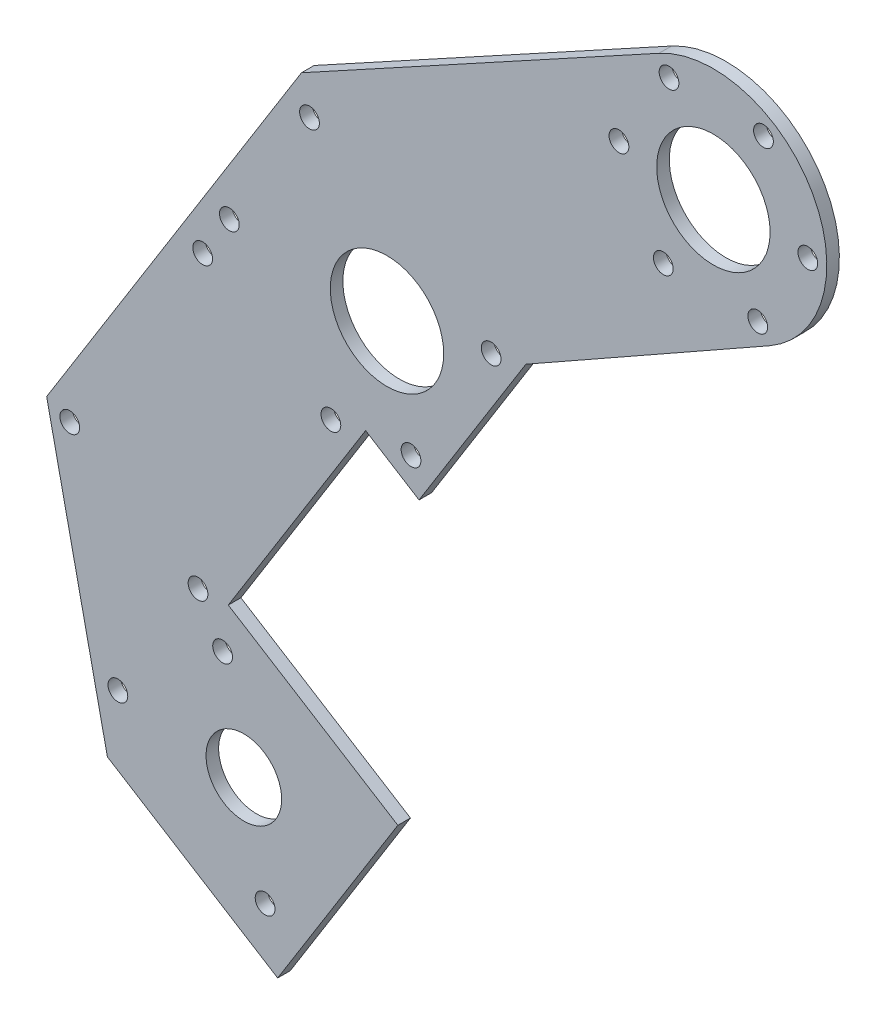
SolidWorks part; units mm, degrees
ref_plane "Front Plane" through (0, 0, 0) normal (0, 0, 1) x (1, 0, 0)
ref_plane "Top Plane" through (0, 0, 0) normal (0, 1, 0) x (1, 0, 0)
ref_plane "Right Plane" through (0, 0, 0) normal (1, 0, 0) x (0, 0, -1)
sketch "Sketch1" plane through (0, 0, -14.1946) normal (0, 0, 1) x (1, 0, 0)
  line L0 (-11.4036, 461.0409) -> (18.8813, 509.5069)
  line L1 (-54.3079, 487.8505) -> (-69.6155, 558.824)
  line L2 (18.8813, 509.5069) -> (-23.8465, 536.2061)
  line L3 (10.7592, 591.5868) -> (-157.4902, 322.3315) construction
  line L4 (-11.4036, 461.0409) -> (-54.3079, 487.8505)
  line L5 (-69.6155, 558.824) -> (-5.4017, 661.5875)
  line L6 (-23.8465, 536.2061) -> (10.7592, 591.5868)
  line L8 (-115.7964, 730.5698) -> (51.1419, 626.2552) construction
  line L9 (-142.7163, 687.4889) -> (24.222, 583.1743) construction
  line L10 (51.1419, 626.2552) -> (112.462, 660.9373)
  line L11 (10.7592, 591.5868) -> (24.222, 583.1743)
  line L13 (24.222, 583.1743) -> (51.1419, 626.2552)
  line L16 (-5.4017, 661.5875) -> (84.678, 710.8773)
  circle A2 centre (16.1415, 618.1747) radius 14.2875
  circle A3 centre (-19.9236, 500.5437) radius 9.525
  circle A5 centre (98.3945, 685.8096) radius 14.2875
  arc A7 (112.462, 660.9373) -> (84.678, 710.8773) centre (98.3945, 685.8096) ccw
  point P33 (98.3945, 685.8096)
extrude "Boss-Extrude1" add sketch "Sketch1" along normal blind 3.175
sketch "Sketch17" plane through (0, 0, -11.0196) normal (0, 0, 1) x (1, 0, 0)
  line L0 (-14.5684, 475.7147) -> (-19.9236, 500.5437)
  line L1 (-19.9236, 500.5437) -> (-25.2787, 525.3728)
  line L2 (16.1415, 618.1747) -> (37.6819, 604.7147) construction
  line L12 (24.222, 583.1743) -> (51.1419, 626.2552) construction
  line L13 (37.6819, 604.7147) -> (27.587, 588.5594) construction
  line L14 (27.587, 588.5594) -> (22.2019, 591.9244) construction
  line L15 (22.2019, 591.9244) -> (-28.9566, 623.8918) construction
  line L16 (-5.4017, 661.5875) -> (-69.6155, 558.824) construction
  line L17 (-28.9566, 623.8918) -> (-23.5715, 620.5268) construction
  line L18 (-23.5715, 620.5268) -> (-3.3816, 652.8374) construction
  line L19 (-3.3816, 652.8374) -> (42.3918, 624.2351) construction
  line L20 (10.7592, 591.5868) -> (5.3741, 594.9518) construction
  line L21 (5.3741, 594.9518) -> (-31.4748, 535.9811) construction
  line L22 (-31.4748, 535.9811) -> (-51.6648, 503.6705) construction
  line L23 (5.3741, 594.9518) -> (2.0091, 589.5667) construction
  line L24 (-31.4748, 535.9811) -> (-63.7855, 556.1711) construction
  line L25 (2.0091, 589.5667) -> (-30.3015, 609.7566) construction
  circle A0 centre (-19.9236, 500.5437) radius 25.4
hole_wizard "#10 Clearance Hole2" positions "Sketch20" profile "Sketch21" hole size "#10" standard "ANSI Inch" end condition through all
sketch "Sketch20" plane through (0, 0, -11.0196) normal (0, 0, 1) x (1, 0, 0)
  point P0 (-25.2787, 525.3728)
  point P3 (-14.5684, 475.7147)
  point P24 (-3.3816, 652.8374)
  point P27 (42.3918, 624.2351)
  point P30 (22.2019, 591.9244)
  point P33 (-23.5715, 620.5268)
  point P42 (-31.4748, 535.9811)
  point P45 (-63.7855, 556.1711)
  point P48 (-51.6648, 503.6705)
  point P54 (2.0091, 589.5667)
  point P57 (-30.3015, 609.7566)
sketch "Sketch21" plane through (-25.2787, 525.3728, -11.0196) normal (1, 0, 0) x (0, -1, 0)
  line L0 (0, 0) -> (0, 3.175)
  line L1 (0, 3.175) -> (2.4892, 3.175)
  line L2 (2.4892, 3.175) -> (2.4892, 0)
  line L5 (2.4892, 0) -> (0, 0)
  line L11 (0, -6.35) -> (0, 107.95) construction
  dimension "Thru Hole Dia." = 4.9784
  dimension "Thru Hole Depth" = 3.175
sketch "Sketch22" plane through (0, 0, -11.0196) normal (0, 0, 1) x (1, 0, 0)
  line L0 (98.3945, 685.8096) -> (111.0132, 706.0038) construction
  line L2 (111.0132, 706.0038) -> (87.2152, 706.8348) construction
  line L3 (87.2152, 706.8348) -> (74.5965, 686.6407) construction
  line L4 (74.5965, 686.6407) -> (85.7758, 665.6155) construction
  line L5 (85.7758, 665.6155) -> (109.5738, 664.7845) construction
  line L6 (109.5738, 664.7845) -> (122.1925, 684.9786) construction
  line L7 (122.1925, 684.9786) -> (111.0132, 706.0038) construction
  circle A0 centre (98.3945, 685.8096) radius 23.8125 construction
hole_wizard "#10 Clearance Hole3" positions "Sketch23" profile "Sketch24" hole size "#10" standard "ANSI Inch" end condition through all
sketch "Sketch23" plane through (0, 0, -11.0196) normal (0, 0, 1) x (1, 0, 0)
  point P0 (111.0132, 706.0038)
  point P3 (122.1925, 684.9786)
  point P6 (109.5738, 664.7845)
  point P9 (85.7758, 665.6155)
  point P12 (74.5965, 686.6407)
  point P15 (87.2152, 706.8348)
sketch "Sketch24" plane through (111.0132, 706.0038, -11.0196) normal (1, 0, 0) x (0, -1, 0)
  line L0 (0, 0) -> (0, 3.175)
  line L1 (0, 3.175) -> (2.4892, 3.175)
  line L2 (2.4892, 3.175) -> (2.4892, 0)
  line L5 (2.4892, 0) -> (0, 0)
  line L11 (0, -6.35) -> (0, 107.95) construction
  dimension "Thru Hole Dia." = 4.9784
  dimension "Thru Hole Depth" = 3.175
